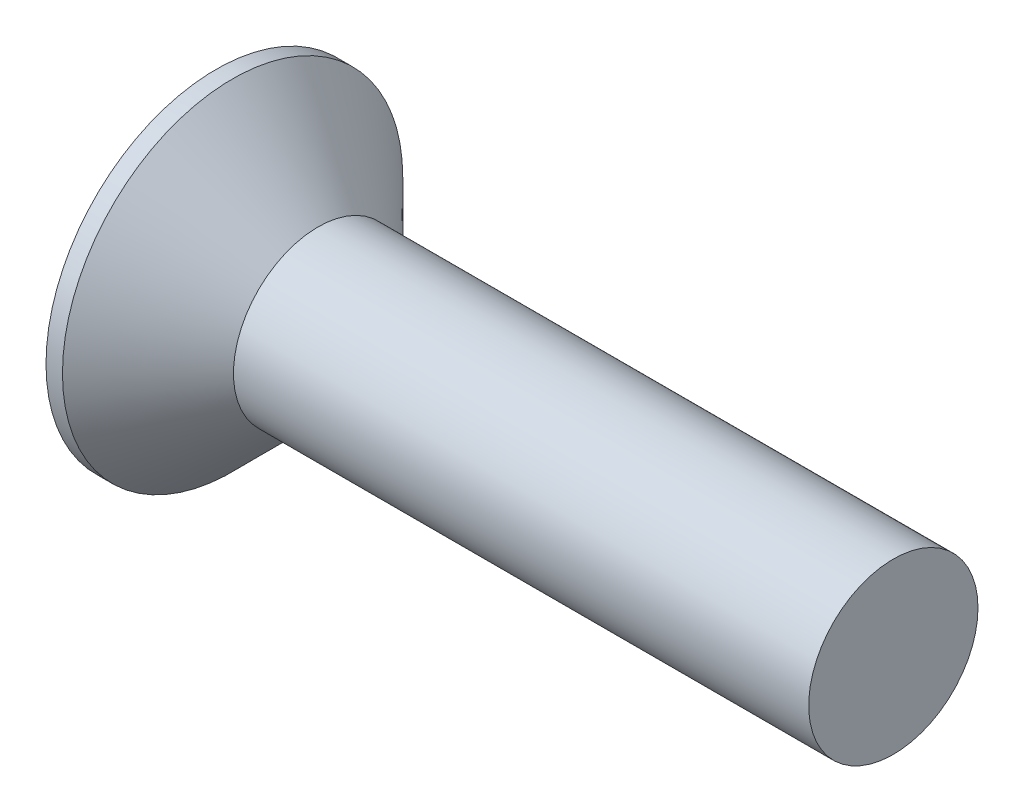
SolidWorks part; units mm, degrees
ref_plane "Front" through (0, 0, 0) normal (0, 0, 1) x (1, 0, 0)
ref_plane "Top" through (0, 0, 0) normal (0, 1, 0) x (1, 0, 0)
ref_plane "Right" through (0, 0, 0) normal (1, 0, 0) x (0, 0, -1)
sketch "Sketch1" plane through (0, 0, 0) normal (0, 0, 1) x (1, 0, 0)
  line L0 (16, 2) -> (4.1879, 2)
  line L1 (4.1879, 2) -> (3.8089, 1.621) construction
  line L2 (2.7, 1.7089) -> (2.4089, 2) construction
  line L3 (0.3889, 4.02) -> (0, 4.02)
  line L4 (16, 2) -> (16, 0)
  line L5 (4.5158, 0) -> (-89.8219, 0) construction
  line L6 (16, 0) -> (0, 0)
  line L7 (0, 4.02) -> (0, 0)
  line L8 (2.9121, 1.621) -> (3.8089, 1.621) construction
  line L9 (4.1879, 2) -> (2.4089, 2)
  line L10 (2.4089, 2) -> (0.3889, 4.02)
  arc A0 (2.9121, 1.621) -> (2.7, 1.7089) centre (2.9121, 1.921) cw construction
  point P11 (2.7879, 1.621)
  dimension "D1" = 45
  dimension "dk" = 8.04
  dimension "l" = 16
  dimension "a" = 1.4
  dimension "D3" = 45
  dimension "k" = 2.7
revolve "Base" add sketch "Sketch1" angle 360 about L5
cosmetic thread "ThreadCosmetic1" parameters "bb"=13.3
dome "BaseTop" faces to dome 1 distance 1 reverse direction no elliptical dome no face at (0, 0, -4.02) parameters "f"=1
ref_plane "Plane1" through (-1, 0, 0) normal (1, 0, 0) x (0, 0, -1)
sketch "Sketch6" plane through (-1, 0, 0) normal (-1, 0, 0) x (0, 0, 1)
  line L0 (-1.9271, 0) -> (2.0512, 0) construction
  line L1 (0, 1.8651) -> (0, -2.0207) construction
  line L2 (0.52, 0.52) -> (0.52, 2.6)
  line L3 (0.52, 2.6) -> (-0.52, 2.6)
  line L4 (-0.52, 0.52) -> (-0.52, 2.6)
  line L5 (0.52, 0.52) -> (2.6, 0.52)
  line L6 (2.6, 0.52) -> (2.6, -0.52)
  line L7 (-2.6, 0.52) -> (-2.6, -0.52)
  line L8 (-0.52, 0.52) -> (-2.6, 0.52)
  line L9 (-0.52, -0.52) -> (-2.6, -0.52)
  line L10 (0.52, -0.52) -> (2.6, -0.52)
  line L11 (-0.52, -0.52) -> (-0.52, -2.6)
  line L12 (0.52, -2.6) -> (-0.52, -2.6)
  line L13 (0.52, -0.52) -> (0.52, -2.6)
  point P16 (-2.6, 0)
  point P17 (2.6, 0)
extrude "CrossRecess" cut sketch "Sketch6" against normal blind 1.35
draft "Draft9" type of draft neutral plane draft angle 30 neutral plane "Plane1" faces to draft 4 face at (-0.1192, 0, -2.6) face at (-0.1192, -2.6, 0) face at (-0.1192, 0, 2.6) face at (-0.1192, 2.6, 0) neutral plane through (-1, 0, 0) neutral plane normal (1, 0, 0) reverse direction yes parameters "D1"=30
fillet "Fillet5" radius 0.3 4 edges at (-0.3092, -0.52, 0.52) (-0.3092, -0.52, -0.52) (-0.3092, 0.52, -0.52) (-0.3092, 0.52, 0.52)
sketch "Sketch7" plane through (-1, 0, 0) normal (-1, 0, 0) x (0, 0, 1)
  line L0 (-2.0126, 0) -> (1.9757, 0) construction
  line L1 (0, 1.9314) -> (0, -2.0126) construction
  line L2 (0, 0) -> (1.5555, 1.5555) construction
  line L3 (0, 0.777) -> (1.8385, 1.8385)
  line L4 (-1.5402, 1.5402) -> (0, 0) construction
  line L5 (0.777, 0) -> (1.8385, 1.8385)
  line L6 (0, -0.777) -> (1.8385, -1.8385)
  line L7 (0.777, 0) -> (1.8385, -1.8385)
  line L8 (-0.777, 0) -> (-1.8385, -1.8385)
  line L9 (0, -0.777) -> (-1.8385, -1.8385)
  line L10 (-0.777, 0) -> (-1.8385, 1.8385)
  line L11 (0, 0.777) -> (-1.8385, 1.8385)
  dimension "D3" = 15
extrude "Cut-Extrude3" [suppressed] cut sketch "Sketch7" against normal blind 10 draft 20
sketch "Sketch8" plane through (0, 0, 0) normal (0, 0, 1) x (1, 0, 0)
  line L0 (-22, 2) -> (-23.75, 1.621)
  line L1 (-23.75, 1.621) -> (2.7879, 1.621)
  line L3 (16, -2) -> (16, 2) construction
  line L4 (2.9121, 1.621) -> (3.8089, 1.621) construction
  line L5 (2.5665, 1.8424) -> (2.7879, 1.621)
  line L6 (2.5665, 1.8424) -> (2.5665, 6.621)
  line L7 (2.5665, 6.621) -> (-22, 6.621)
  line L8 (-22, 6.621) -> (-22, 2)
  line L9 (62.4753, 0) -> (52.9594, 0) construction
  line L10 (2.7, 1.7089) -> (2.4089, 2) construction
  dimension "D1" = 5
  dimension "x" = 1.75
sketch "Sketch9" plane through (0, 0, 0) normal (0, 0, 1) x (1, 0, 0)
  line L0 (16, 1.6718) -> (16.1895, 2)
  line L1 (16.1895, 2) -> (16.1895, 2.379)
  line L2 (16.1895, 2.379) -> (15.8105, 2.379)
  line L3 (15.8105, 2.379) -> (15.8105, 2)
  line L4 (15.8105, 2) -> (16, 1.6718)
  line L5 (16, -2) -> (16, 2) construction
  line L6 (0, 0) -> (66.6901, 0) construction
  dimension "D2" = 0.379
revolve "Cut-Revolve10" [suppressed] cut sketch "Sketch9" angle 360 about L6
pattern_linear "LPattern10" [suppressed] count 29 spacing 0.4548 along (-1, 0, 0) of bodies 105
equation "\"D1@Sketch6\" = \"m@Sketch6\" / 5"
equation "\"D1@CrossRecess\" = \"k@Sketch1\" / 2"
equation "\"D1@Plane1\" = \"f@BaseTop\""
equation "\"D1@Sketch9\" = \"d@Sketch1\""
equation "\"D2@Sketch9\" =  ( \"d@Sketch1\" - \"THD_MINOR@ThreadCosmetic1\" )  / 2"
equation "\"D3@LPattern10\" = \"D2@Sketch9\" * 1.2"
equation "\"D1@LPattern10\" = \"bb@ThreadCosmetic1\" / \"D3@LPattern10\" "
